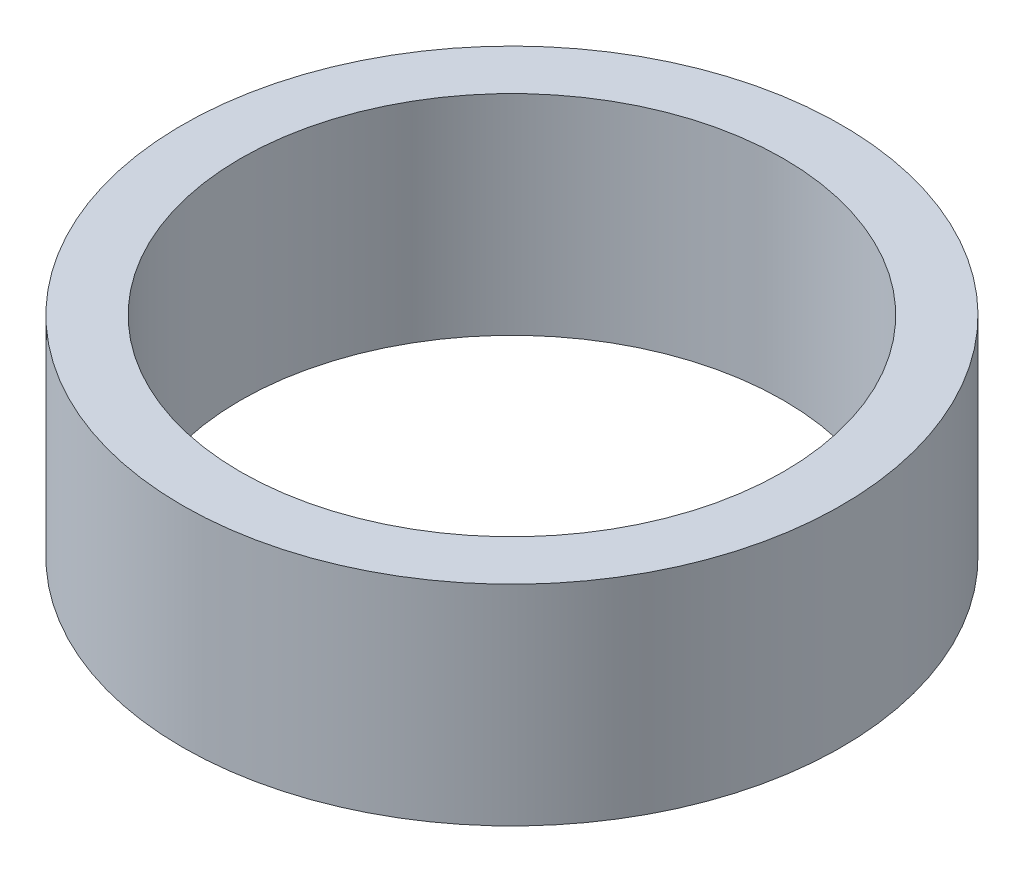
SolidWorks part; units mm, degrees
ref_plane "Front Plane" through (0, 0, 0) normal (0, 0, 1) x (1, 0, 0)
ref_plane "Top Plane" through (0, 0, 0) normal (0, 1, 0) x (1, 0, 0)
ref_plane "Right Plane" through (0, 0, 0) normal (1, 0, 0) x (0, 0, -1)
sketch "Sketch1" plane through (0, 0, 0) normal (0, 1, 0) x (1, 0, 0)
  circle A0 centre (0, 0) radius 42.5
  dimension "FLANGE_OD" = 85
extrude "Boss-Extrude1" add sketch "Sketch1" along normal blind 27
sketch "Sketch2" plane through (0, 0, 0) normal (0, 1, 0) x (1, 0, 0)
  circle A0 centre (0, 0) radius 35
  dimension "BORE_D" = 70
extrude "Cut-Extrude1" cut sketch "Sketch2" along normal through all
sketch "Sketch3" plane through (0, 27, 0) normal (0, 1, 0) x (1, 0, 0)
  circle A0 centre (0, 0) radius 19.2558 construction
  circle A1 centre (-19.2558, 0) radius 1.5
  dimension "BOLT_D" = 3
  dimension "BOLT_PCD" = 38.5116
extrude "Cut-Extrude2" cut sketch "Sketch3" against normal blind 26.0579 rebuild error yes
pattern_circular "CirPattern1" count 4 over 360 rebuild error yes
